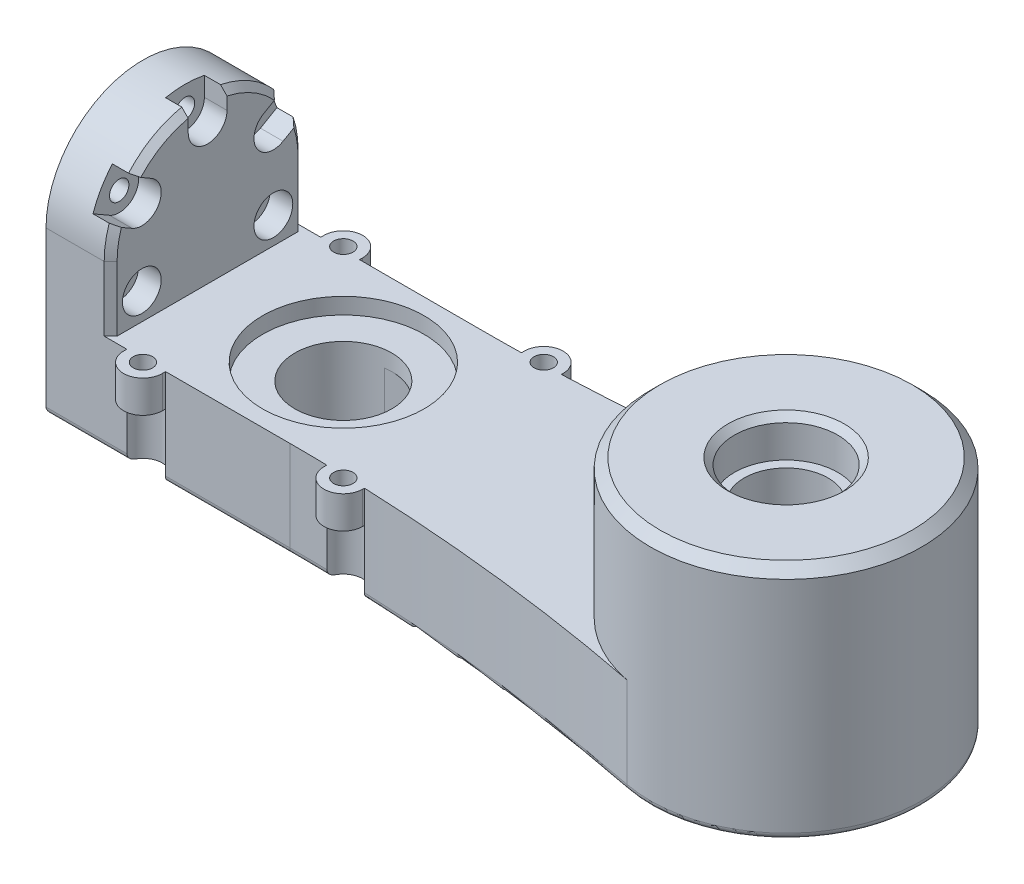
SolidWorks part; units mm, degrees
ref_plane "Front Plane" through (0, 0, 0) normal (0, 0, 1) x (1, 0, 0)
ref_plane "Top Plane" through (0, 0, 0) normal (0, 1, 0) x (1, 0, 0)
ref_plane "Right Plane" through (0, 0, 0) normal (1, 0, 0) x (0, 0, -1)
sketch "Sketch1" plane through (0, 0, 0) normal (0, 1, 0) x (1, 0, 0)
  line L1 (-66.3274, 15.3319) -> (44.1726, 15.3319)
  line L4 (44.1726, 15.3319) -> (44.1726, -14.6681)
  line L5 (-66.3274, 15.3319) -> (-66.3274, 0.3319) construction
  line L8 (-66.3274, 15.3319) -> (-66.3274, -14.6681)
  line L9 (-66.3274, -14.6681) -> (44.1726, -14.6681)
  line L10 (-45.3274, 0.3319) -> (23.1726, 0.3319) construction
  line L12 (23.1726, 0.3319) -> (44.1726, 0.3319) construction
  line L14 (-66.3274, 0.3319) -> (-24.3274, 0.3319) construction
  circle A3 centre (-45.3274, 0.3319) radius 7.5
  dimension "D13" = 15
  dimension "D2" = 68.5
  dimension "D3" = 21
  dimension "D12" = 42
extrude "Boss-Extrude1" add sketch "Sketch1" along normal blind 15
sketch "Sketch5" plane through (0, 0, 0) normal (0, -1, 0) x (1, 0, 0)
  line L0 (44.1726, -0.3319) -> (23.1726, -0.3319) construction
  line L1 (44.1726, 14.6681) -> (44.1726, -15.3319) construction
  circle A0 centre (23.1726, -0.3319) radius 21
  dimension "D2" = 42
  dimension "D1" = 21
extrude "Boss-Extrude2" add sketch "Sketch5" against normal blind 15
sketch "Sketch7" plane through (0, 0, 0) normal (0, -1, 0) x (1, 0, 0)
  line L0 (-46.3706, 8.9989) -> (21.2837, 16.5629) construction
  line L1 (21.2837, -17.2266) -> (-46.3706, -9.6626) construction
  line L2 (-45.3274, -0.3319) -> (23.1726, -0.3319) construction
  circle A0 centre (23.1726, -0.3319) radius 17
  circle A1 centre (-45.3274, -0.3319) radius 9.3889 construction
  dimension "D1" = 34
  dimension "D2" = 68.5
extrude "Cut-Extrude2" cut sketch "Sketch7" against normal blind 15
sketch "Sketch9" plane through (0, 0, 0) normal (0, -1, 0) x (1, 0, 0)
  line L6 (-46.3676, 7.0957) -> (20.8149, 16.5039)
  line L7 (-46.3676, -7.7594) -> (20.8149, -17.1676)
  arc A3 (-46.3676, 7.0957) -> (-46.3676, -7.7594) centre (-45.3274, -0.3319) ccw
  arc A4 (20.8149, -17.1676) -> (20.8149, 16.5039) centre (23.1726, -0.3319) ccw
  dimension "D1" = 34
  dimension "D2" = 7.5
extrude "Cut-Extrude4" cut sketch "Sketch9" against normal blind 9
sketch "Sketch11" plane through (0, 15, 0) normal (0, 1, 0) x (1, 0, 0)
  circle A0 centre (23.1726, 0.3319) radius 17
  circle A1 centre (23.1726, 0.3319) radius 21
  dimension "D1" = 42
  dimension "D2" = 34
extrude "Boss-Extrude3" add sketch "Sketch11" along normal blind 21.5
chamfer "Chamfer3" distance 1.5 angle 45 1 edges at (23.1726, 36.5, 20.6681)
sketch "Sketch29" plane through (0, 0, 0) normal (1, 0, 0) x (0, 0, -1)
  line L0 (0.3319, 0) -> (0.3319, 14) construction
  line L1 (-14.6681, 0) -> (15.3319, 0) construction
  dimension "D1" = 14
ref_plane "Plane2" through (0, 14, -0.3319) normal (0, 1, 0) x (1, 0, 0)
sketch "Sketch31" plane through (0, 14, -0.3319) normal (0, 1, 0) x (1, 0, 0)
  circle A0 centre (23.1726, 0) radius 18.1679
  circle A1 centre (23.1726, 0) radius 6.5
  dimension "D1" = 13
extrude "Boss-Extrude4" add sketch "Sketch31" along normal blind 16.5
sketch "Sketch32" plane through (0, 30.5, 0) normal (0, 1, 0) x (1, 0, 0)
  circle A0 centre (23.1726, 0.3319) radius 8
  circle A1 centre (23.1726, 0.3319) radius 17
  dimension "D1" = 16
extrude "Boss-Extrude5" add sketch "Sketch32" along normal blind 6
chamfer "Chamfer4" distance 1 angle 45 1 edges at (23.1726, 36.5, 7.6681)
chamfer "Chamfer7" distance 1 angle 45 1 edges at (-37.8274, 9, -0.3319)
sketch "Sketch33" plane through (0, 14, 0) normal (0, -1, 0) x (1, 0, 0)
  circle A0 centre (23.1726, -0.3319) radius 8
  dimension "D1" = 16
extrude "Cut-Extrude13" cut sketch "Sketch33" against normal blind 7
sketch "Sketch34" plane through (0, 15, 0) normal (0, 1, 0) x (1, 0, 0)
  circle A0 centre (-45.3274, 0.3319) radius 12.5
  dimension "D1" = 25
extrude "Cut-Extrude14" cut sketch "Sketch34" against normal blind 2.5
fillet "Fillet2" radius 300 2 edges at (8.4756, 12, 14.6681) (8.4756, 12, -15.3319)
sketch "Sketch35" plane through (0, 0, 0) normal (0, -1, 0) x (1, 0, 0)
  line L1 (37.8695, 14.6681) -> (54.8737, 14.6681)
  line L3 (37.8695, -15.3319) -> (54.8737, -15.3319)
  line L4 (54.8737, 14.6681) -> (54.8737, -15.3319)
  arc A1 (37.8695, -15.3319) -> (37.8695, 14.6681) centre (23.1726, -0.3319) ccw
  dimension "D1" = 30
extrude "Cut-Extrude15" cut sketch "Sketch35" against normal blind 21.5
sketch "Sketch36" plane through (-66.3274, 0, 0) normal (-1, 0, 0) x (0, 0, 1)
  line L0 (14.6681, 0) -> (-0.3319, 0) construction
  line L1 (-15.3319, 0) -> (14.6681, 0) construction
  line L2 (-0.3319, 0) -> (-0.3319, 25) construction
  line L5 (-15.3319, 25) -> (-15.3319, 0)
  line L6 (-15.3319, 0) -> (14.6681, 0)
  line L7 (14.6681, 25) -> (14.6681, 0)
  arc A0 (14.6681, 25) -> (-15.3319, 25) centre (-0.3319, 25) ccw
  dimension "D2" = 30
  dimension "D1" = 25
extrude "Boss-Extrude6" add sketch "Sketch36" along normal blind 10
sketch "Sketch37" plane through (-76.3274, 0, 0) normal (-1, 0, 0) x (0, 0, 1)
  line L0 (-0.3319, 25) -> (-0.3319, 36.75) construction
  line L1 (-10.5077, 30.875) -> (-0.3319, 25) construction
  line L2 (-0.3319, 25) -> (-10.5077, 19.125) construction
  line L3 (9.8439, 30.875) -> (-0.3319, 25) construction
  line L4 (-0.3319, 25) -> (9.8439, 19.125) construction
  circle A0 centre (-0.3319, 25) radius 11.75 construction
  circle A1 centre (-0.3319, 36.75) radius 1.5
  circle A2 centre (-10.5077, 30.875) radius 1.5
  circle A3 centre (-10.5077, 19.125) radius 1.5
  circle A4 centre (9.8439, 19.125) radius 1.5
  circle A5 centre (9.8439, 30.875) radius 1.5
  dimension "D1" = 23.5
  dimension "D6" = 3
  dimension "D2" = 60
  dimension "D3" = 60
  dimension "D4" = 60
  dimension "D5" = 60
extrude "Cut-Extrude16" cut sketch "Sketch37" against normal blind 10
sketch "Sketch38" plane through (-66.3274, 0, 0) normal (1, 0, 0) x (0, 0, -1)
  line L0 (-9.8439, 30.875) -> (0.3319, 25) construction
  line L1 (0.3319, 25) -> (10.5077, 30.875) construction
  line L2 (-11.3439, 28.2769) -> (-18.7189, 32.5348)
  line L3 (-18.7189, 32.5348) -> (-15.2239, 37.4452)
  line L4 (-15.2239, 37.4452) -> (-8.3439, 33.4731)
  line L5 (9.0077, 33.4731) -> (14.4955, 36.6415)
  line L7 (-2.6681, 36.75) -> (-2.6681, 41.8047)
  line L8 (-2.6681, 41.8047) -> (3.3319, 41.8047)
  line L9 (3.3319, 36.75) -> (3.3319, 41.8047)
  line L10 (14.4955, 36.6415) -> (17.2283, 31.291)
  line L11 (17.2283, 31.291) -> (12.0077, 28.2769)
  circle A0 centre (-9.8439, 19.125) radius 3
  circle A1 centre (10.5077, 19.125) radius 3
  arc A2 (-11.3439, 28.2769) -> (-8.3439, 33.4731) centre (-9.8439, 30.875) ccw
  arc A3 (-2.6681, 36.75) -> (3.3319, 36.75) centre (0.3319, 36.75) ccw
  arc A4 (9.0077, 33.4731) -> (12.0077, 28.2769) centre (10.5077, 30.875) ccw
  dimension "D1" = 6
extrude "Cut-Extrude17" cut sketch "Sketch38" against normal blind 3.5
fillet "Fillet3" radius 1 6 edges at (-57.4643, 0, 14.6681) (-9.5991, 0, 16.0733) (44.1726, 0, -0.3319) (-9.5991, 0, -16.737) (-76.3274, 0, -0.3319) (-57.4643, 0, -15.3319)
chamfer "Chamfer9" distance 1 angle 45 6 edges at (-66.3274, 27.4064, 14.4739) (-66.3274, 20, 14.6681) (-66.3274, 37.9904, 7.1681) (-66.3274, 37.9904, -7.8319) (-66.3274, 27.4064, -15.1376) (-66.3274, 20, -15.3319)
sketch "Sketch39" plane through (0, 15, 0) normal (0, 1, 0) x (1, 0, 0)
  line L1 (-60.8274, 15.8319) -> (-29.8274, 15.8319) construction
  line L2 (-60.8274, 15.8319) -> (-60.8274, -15.1681) construction
  line L3 (-60.8274, -15.1681) -> (-29.8274, -15.1681) construction
  line L4 (-29.8274, 15.8319) -> (-29.8274, -15.1681) construction
  line L6 (-63.8274, 15.8319) -> (-63.8274, 12.4296)
  line L7 (-63.8274, 12.4296) -> (-57.8274, 12.4296)
  line L8 (-57.8274, 15.8319) -> (-57.8274, 12.4296)
  line L10 (-32.8274, 15.8319) -> (-32.8274, 12.0688)
  line L11 (-32.8274, 12.0688) -> (-26.8274, 12.0688)
  line L12 (-26.8274, 15.8319) -> (-26.8274, 12.0688)
  line L14 (-63.8274, -15.1681) -> (-63.8274, -10.424)
  line L15 (-63.8274, -10.424) -> (-57.8274, -10.424)
  line L16 (-57.8274, -15.1681) -> (-57.8274, -10.424)
  line L18 (-32.8274, -15.1681) -> (-32.8274, -10.424)
  line L19 (-32.8274, -10.424) -> (-26.8274, -10.424)
  line L20 (-26.8274, -15.1681) -> (-26.8274, -10.424)
  circle A0 centre (-45.3274, 0.3319) radius 15.5 construction
  arc A1 (-57.8274, 15.8319) -> (-63.8274, 15.8319) centre (-60.8274, 15.8319) ccw
  arc A2 (-26.8274, 15.8319) -> (-32.8274, 15.8319) centre (-29.8274, 15.8319) ccw
  arc A3 (-32.8274, -15.1681) -> (-26.8274, -15.1681) centre (-29.8274, -15.1681) ccw
  arc A4 (-63.8274, -15.1681) -> (-57.8274, -15.1681) centre (-60.8274, -15.1681) ccw
  dimension "D1" = 31
  dimension "D2" = 6
  dimension "D3" = 6
  dimension "D4" = 6
  dimension "D5" = 6
extrude "Boss-Extrude7" add sketch "Sketch39" against normal blind 5
sketch "Sketch40" plane through (0, 15, 0) normal (0, 1, 0) x (1, 0, 0)
  circle A0 centre (-60.8274, 15.8319) radius 1.5
  dimension "D1" = 3
extrude "Cut-Extrude18" cut sketch "Sketch40" against normal blind 21
pattern_circular "CirPattern1" count 4 over 360 about axis through (-45.3274, 0, -0.3319) along (0, 1, 0) of "Cut-Extrude18"
sketch "Sketch41" plane through (0, 0, 0) normal (0, -1, 0) x (1, 0, 0)
  circle A0 centre (-60.8274, 15.1681) radius 3
  dimension "D1" = 6
extrude "Cut-Extrude19" cut sketch "Sketch41" against normal blind 10
pattern_circular "CirPattern2" count 4 over 360 about axis through (-45.3274, 0, -0.3319) along (0, 1, 0) of "Cut-Extrude19"
sketch "Sketch43" plane through (0, 14, 0) normal (0, -1, 0) x (1, 0, 0)
  circle A0 centre (23.1726, -0.3319) radius 8
  circle A1 centre (23.1726, -0.3319) radius 17
extrude "Cut-Extrude20" cut sketch "Sketch43" against normal blind 2
chamfer "Chamfer10" distance 1 angle 45 1 edges at (23.1726, 16, -8.3319)
sketch "Sketch46" plane through (0, 0, 0) normal (0, -1, 0) x (1, 0, 0)
  line L0 (23.1726, -0.3319) -> (40.1726, -0.3319) construction
  line L1 (40.1726, -0.3319) -> (43.1726, -0.3319) construction
  line L2 (-52.8274, -0.3319) -> (-54.8274, -0.3319) construction
  line L3 (43.1726, -0.3319) -> (-54.8274, -0.3319) construction
  line L4 (-46.7727, 8.5513) -> (19.9609, 19.4086) construction
  line L5 (-54.8274, -0.3319) -> (-57.8274, -0.3319) construction
  arc A0 (20.8149, -17.1676) -> (20.8149, 16.5039) centre (23.1726, -0.3319) ccw construction
  arc A1 (19.3237, -19.958) -> (19.3237, 19.2943) centre (23.1726, -0.3319) ccw construction
  circle A2 centre (41.6726, -0.3319) radius 0.8
  arc A3 (-46.3676, 7.0957) -> (-46.3676, -7.7594) centre (-45.3274, -0.3319) ccw construction
  circle A4 centre (-54.8274, -0.3319) radius 0.8
  circle A5 centre (23.1726, -0.3319) radius 20 construction
  circle A6 centre (-45.3274, -0.3319) radius 9 construction
  circle A7 centre (23.1726, -0.3319) radius 17 construction
  dimension "D1" = 1.6
  dimension "D3" = 1.6
  dimension "D5" = 40
  dimension "D6" = 18
  dimension "D10" = 34
  dimension "D2" = 2
  dimension "D4" = 3
  dimension "D7" = 101
  dimension "D8" = 1.5
  dimension "D9" = 68.5
extrude "Cut-Extrude21" cut sketch "Sketch46" against normal blind 5
thread "Thread1" pitch 0.4 start angle 0, offset 1, length 0, pitch 0.4, diameter 1.6
ref_plane "Plane4" through (-54.0274, -1, -0.3319) normal (0, 0, 1) x (1, 0, 0)
sketch "Thread Profile2" plane through (-54.0274, -1, -0.3319) normal (0, 0, 1) x (1, 0, 0)
  line L0 (0, 0) -> (0, 0.4) construction
  line L1 (0, 0) -> (0.2165, 0.125)
  line L2 (0.2165, 0.125) -> (0.2165, 0.175)
  line L3 (0.2165, 0.175) -> (0, 0.3)
  line L4 (0.2165, 0.15) -> (0, 0.15) construction
  line L11 (0, 0) -> (0, 0.3)
  point P2 (0, 0)
  dimension "Pitch" = 0.4
  dimension "Profile_Angle" = 60
  dimension "Profile_Land" = 0.05
  dimension "Profile_Height" = 0.2165
thread "Thread2" pitch 0.4 profile "Thread Profile3" start angle 0, offset 1, length 0, pitch 0.4, diameter 1.6
ref_plane "Plane5" through (42.4726, -1, -0.3319) normal (0, 0, 1) x (1, 0, 0)
sketch "Thread Profile3" plane through (42.4726, -1, -0.3319) normal (0, 0, 1) x (1, 0, 0)
  line L0 (0, 0) -> (0, 0.4) construction
  line L1 (0, 0) -> (0.2165, 0.125)
  line L2 (0.2165, 0.125) -> (0.2165, 0.175)
  line L3 (0.2165, 0.175) -> (0, 0.3)
  line L4 (0.2165, 0.15) -> (0, 0.15) construction
  line L11 (0, 0) -> (0, 0.3)
  point P2 (0, 0)
  dimension "Pitch" = 0.4
  dimension "Profile_Angle" = 60
  dimension "Profile_Land" = 0.05
  dimension "Profile_Height" = 0.2165
